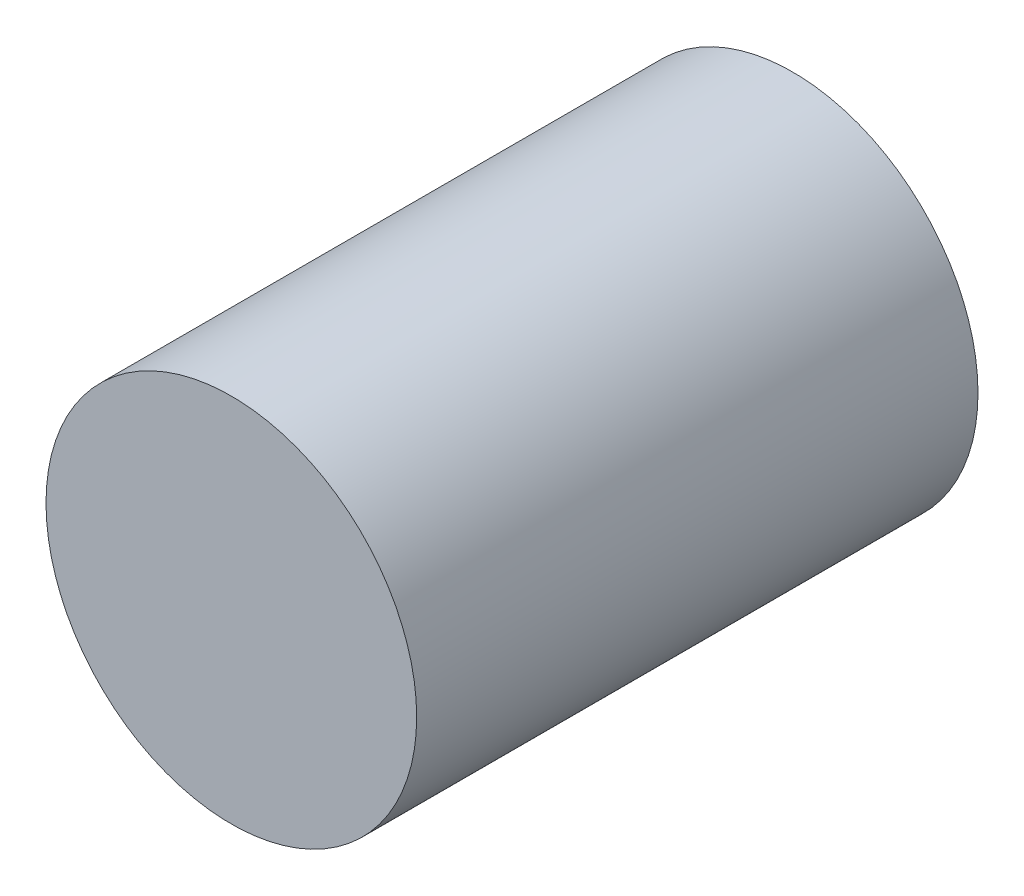
SolidWorks part; units mm, degrees
material "PVC 0.007 Plasticized"
ref_plane "Front Plane" through (0, 0, 0) normal (0, 0, 1) x (1, 0, 0)
ref_plane "Top Plane" through (0, 0, 0) normal (0, 1, 0) x (1, 0, 0)
ref_plane "Right Plane" through (0, 0, 0) normal (1, 0, 0) x (0, 0, -1)
sketch "Sketch1" plane through (0, 0, 0) normal (0, 0, 1) x (1, 0, 0)
  circle A0 centre (0, 0) radius 87.5
  dimension "D1" = 175
extrude "Boss-Extrude1" add sketch "Sketch1" along normal blind 132.5 contours A0
extrude "Boss-Extrude2" add sketch "Sketch1<3>" against normal blind 132.5
sketch "Sketch1<3>" plane through (0, 0, 0) normal (0, 0, 1) x (1, 0, 0) same geometry as "Sketch1"
